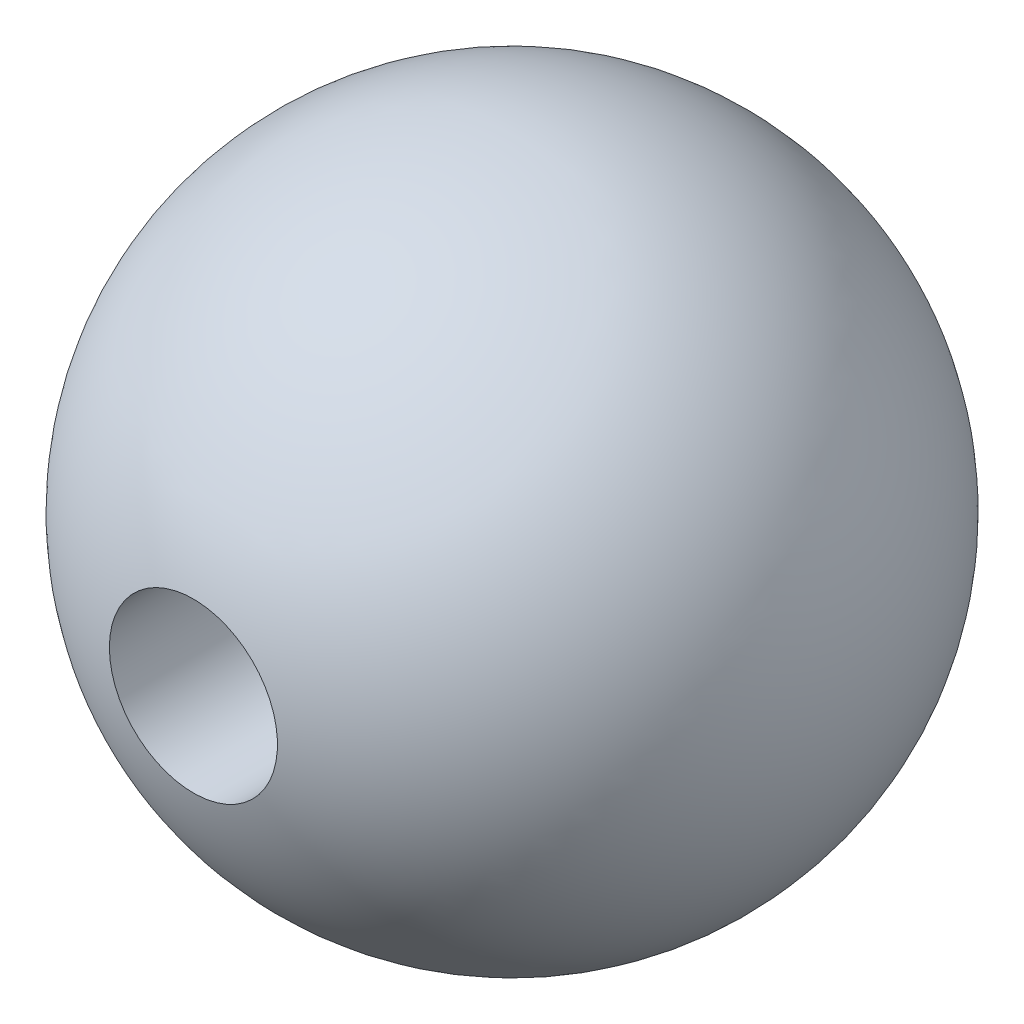
SolidWorks part; units mm, degrees
ref_plane "Front Plane" through (0, 0, 0) normal (0, 0, 1) x (1, 0, 0)
ref_plane "Top Plane" through (0, 0, 0) normal (0, 1, 0) x (1, 0, 0)
ref_plane "Right Plane" through (0, 0, 0) normal (1, 0, 0) x (0, 0, -1)
sketch "Sketch1" plane through (0, 0, 0) normal (0, 0, 1) x (1, 0, 0)
  line L0 (0, 0) -> (0, 12.7) construction
  line L1 (0, 12.7) -> (0, -12.7)
  arc A1 (0, 12.7) -> (0, -12.7) centre (0, 0) ccw
  dimension "D1" = 12.7
revolve "Revolve3" add sketch "Sketch1" angle 360 about L0
sketch "Sketch2" plane through (0, 0, 0) normal (0, 0, 1) x (1, 0, 0)
  circle A0 centre (0, 0) radius 3.2385
  dimension "D1" = 6.477
extrude "Cut-Extrude1" cut sketch "Sketch2" against normal through all both and the other way through all
